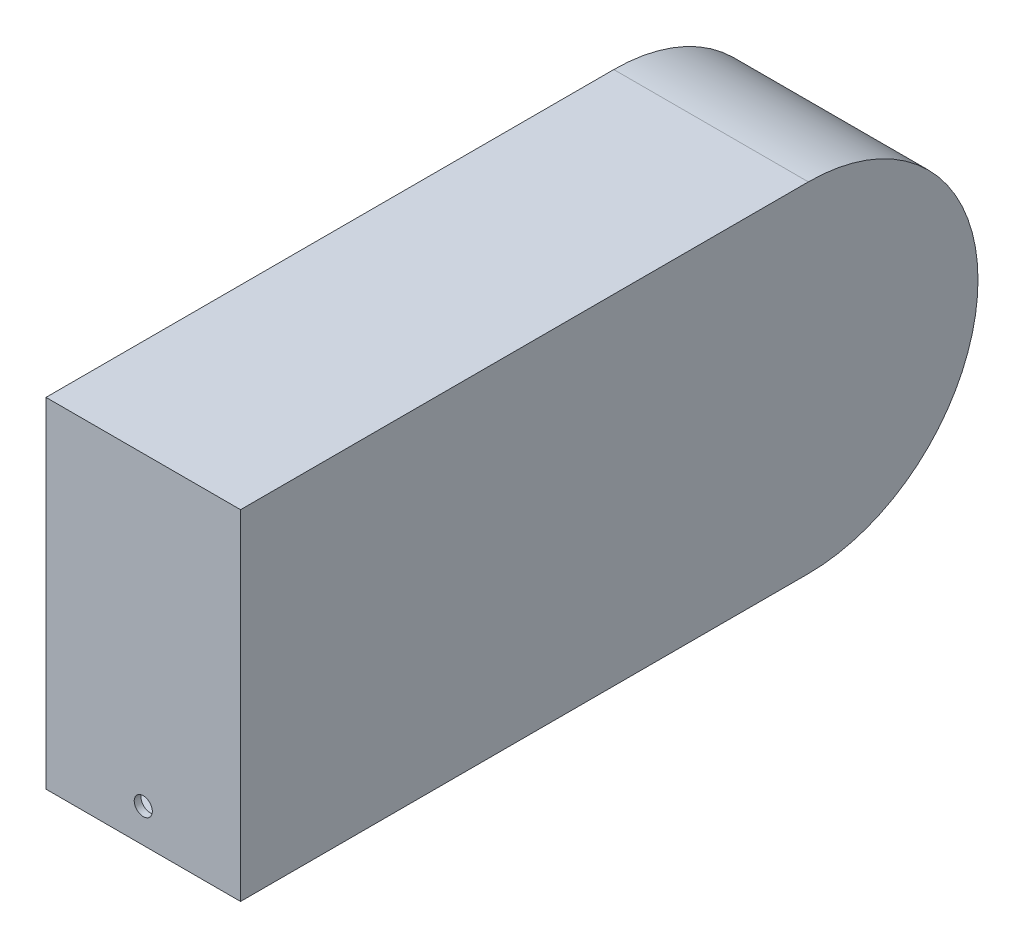
SolidWorks part; units mm, degrees
other "Markup1"
sketch "Sketch10" plane through (68.2625, 233.3625, 398.4625) normal (0.4688, 0.3088, 0.8276) x (0.8055, 0.235, -0.5439)
ref_plane "Front Plane" through (0, 0, 0) normal (0, 0, 1) x (1, 0, 0)
ref_plane "Top Plane" through (0, 0, 0) normal (0, 1, 0) x (1, 0, 0)
ref_plane "Right Plane" through (0, 0, 0) normal (1, 0, 0) x (0, 0, -1)
sketch "Sketch2" plane through (0, 0, 0) normal (1, 0, 0) x (0, 0, -1)
  line L0 (0, 0) -> (-393.7, 0)
  line L1 (-393.7, 0) -> (-393.7, 228.6)
  line L2 (-393.7, 228.6) -> (0, 228.6)
  line L4 (0, -4.7625) -> (-398.4625, -4.7625)
  line L5 (-398.4625, -4.7625) -> (-398.4625, 233.3625)
  line L6 (-398.4625, 233.3625) -> (0, 233.3625)
  arc A0 (0, 0) -> (0, 228.6) centre (0, 114.3) ccw
  arc A1 (0, -4.7625) -> (0, 233.3625) centre (0, 114.3) ccw
  dimension "D1" = 228.6
  dimension "D3" = 393.7
  dimension "D2" = 4.7625
extrude "Boss-Extrude1" add sketch "Sketch2" along normal blind 63.5 and the other way blind 63.5
sketch "Sketch4" plane through (0, 0, 398.4625) normal (0, 0, 1) x (1, 0, 0)
  line L0 (0, -130.9688) -> (0, 130.9688) construction
  line L3 (69.85, 0) -> (-69.85, 0) construction
  circle A0 centre (0, 19.05) radius 6.35
  point P2 (0, 0)
  point P5 (0, 0)
  point P6 (0, 0)
  point P7 (0, 0)
  point P10 (0, 0)
  point P11 (0, 0)
  dimension "D1" = 12.7
  dimension "D2" = 19.05
extrude "Cut-Extrude1" cut sketch "Sketch4" against normal up to next
sketch "Sketch9" plane through (63.5, 0, 0) normal (1, 0, 0) x (0, 0, -1)
  line L0 (0, 69.85) -> (0, -69.85) construction
  line L1 (-398.4625, 233.3625) -> (0, 233.3625)
  line L2 (-398.4625, 233.3625) -> (-398.4625, -4.7625)
  line L3 (-398.4625, -4.7625) -> (0, -4.7625)
  arc A0 (0, -4.7625) -> (0, 233.3625) centre (0, 114.3) ccw
  arc A1 (0, -4.7625) -> (0, 233.3625) centre (0, 114.3) ccw construction
extrude "Boss-Extrude3" add sketch "Sketch9" along normal blind 4.7625
mirror "Mirror1" about plane through (0, 0, 0) normal (1, 0, 0) of "Boss-Extrude3"
equation "\"fuselage_height\"=9"
equation "\"D1@Sketch2\"=\"fuselage_height\""
equation "\"fuselage_length\"=15.5"
equation "\"D3@Sketch2\"= \"fuselage_length\""
